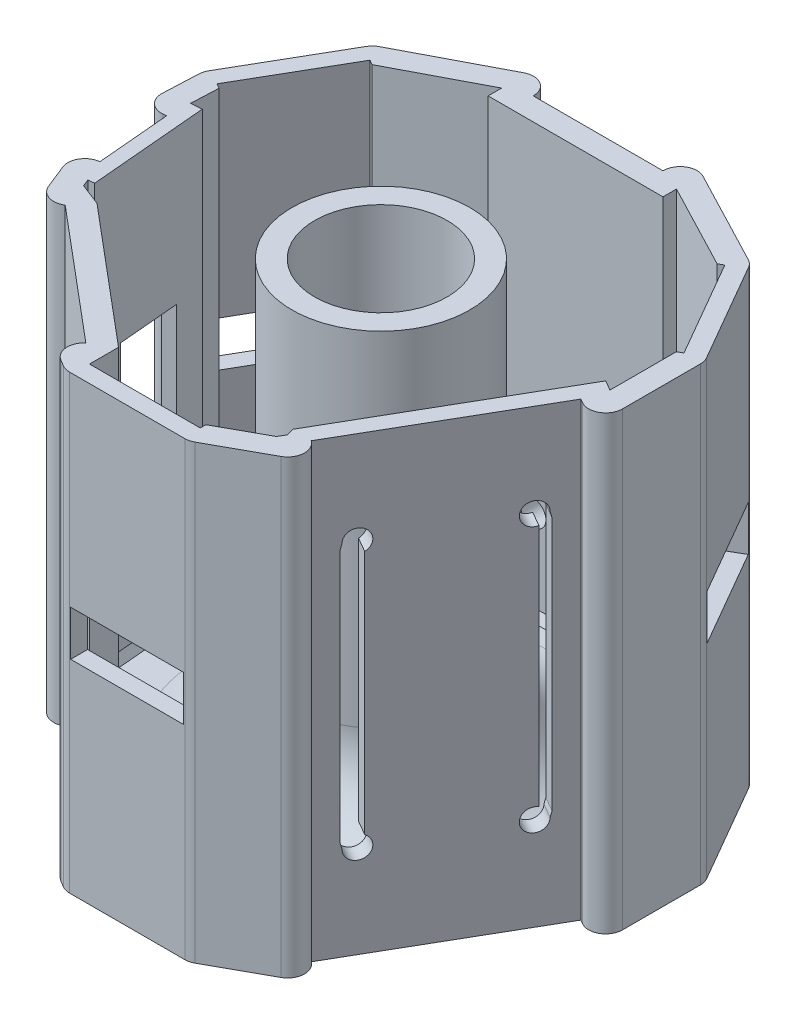
SolidWorks part; units mm, degrees
ref_plane "Alzado" through (0, 0, 0) normal (0, 0, 1) x (1, 0, 0)
ref_plane "Planta" through (0, 0, 0) normal (0, 1, 0) x (1, 0, 0)
ref_plane "Vista lateral" through (0, 0, 0) normal (1, 0, 0) x (0, 0, -1)
sketch "Croquis1" plane through (0, 0, 0) normal (0, 1, 0) x (1, 0, 0)
  line L0 (0, 0) -> (0, 45) construction
  line L8 (0, 0) -> (0, -45) construction
  line L9 (0, 0) -> (38.9711, 22.5) construction
  line L10 (0, 0) -> (-38.9711, 22.5) construction
  line L12 (-44.4711, 12.9737) -> (-33.4711, 32.0263)
  line L13 (33.4711, 32.0263) -> (44.4711, 12.9737)
  line L14 (-11, -45) -> (11, -45)
  line L19 (0, 0) -> (38.9711, -22.5) construction
  line L24 (0, 0) -> (-28.9254, -34.472) construction
  line L26 (0, 0) -> (-44.8288, -3.922) construction
  line L28 (44.4664, -6.9091) -> (44.4711, 12.9737)
  line L29 (33.4711, 32.0263) -> (11.5, 43.5057)
  line L30 (-11.5, 43.5057) -> (-33.4711, 32.0263)
  line L31 (-44.4711, 12.9737) -> (-44.9252, 2.5944)
  line L32 (-38.7871, -22.8159) -> (-43.7921, -10.3561)
  line L33 (-11, -45) -> (-15.827, -42.1249)
  line L34 (11, -45) -> (26.066, -36.682)
  line L36 (26.066, -36.682) -> (21.7702, -34.1233)
  line L37 (21.7702, -34.1233) -> (39.2695, -3.8137)
  line L38 (39.2695, -3.8137) -> (44.4664, -6.9091)
  line L39 (-38.7871, -22.8159) -> (-36.2125, -19.7545)
  line L40 (-36.2125, -19.7545) -> (-13.2559, -39.0607)
  line L41 (-13.2559, -39.0607) -> (-15.827, -42.1249)
  line L42 (-44.9252, 2.5944) -> (-40.9404, 2.943)
  line L43 (-40.9404, 2.943) -> (-39.8073, -10.0075)
  line L44 (-39.8073, -10.0075) -> (-43.7921, -10.3561)
  line L45 (-11.5, 43.5057) -> (-11.5, 38.5057)
  line L46 (-11.5, 38.5057) -> (11.5, 38.5057)
  line L47 (11.5, 38.5057) -> (11.5, 43.5057)
  circle A0 centre (0, 0) radius 45 construction
  circle A1 centre (0, 0) radius 11.75
  point P7 (-38.9711, 22.5)
  point P15 (0, 45)
  point P17 (38.9711, 22.5)
  point P20 (0, -45)
  point P31 (-28.9254, -34.472)
  point P35 (-44.8288, -3.922)
  point P38 (-40.3739, -3.5323)
  dimension "D1" = 90
  dimension "D2" = 23.5
  dimension "D13" = 4
  dimension "D3" = 120
  dimension "D4" = 120
  dimension "D5" = 23
  dimension "D6" = 22
  dimension "D7" = 22
  dimension "D8" = 22
  dimension "D9" = 35
  dimension "D10" = 5
  dimension "D11" = 34.9985
  dimension "D12" = 30
  dimension "D14" = 40
  dimension "D15" = 35
  dimension "D16" = 29.9956
  dimension "D17" = 4
  dimension "D18" = 13
  dimension "D19" = 23
  dimension "D20" = 5
extrude "Saliente-Extruir2" add sketch "Croquis1" along normal blind 80
shell "Vaciado1" thickness 4 removed face at (-6.4534, 80, 2.5494)
sketch "Croquis3" plane through (-40.3739, 0, 3.5323) normal (-0.9962, 0, 0.0872) x (0.0872, 0, 0.9962)
  line L0 (0, 80) -> (0, 40) construction
  line L2 (-6.5, 80) -> (6.5, 80) construction
  line L8 (5.5, 27.25) -> (-5.5, 27.25)
  line L9 (5.5, 27.25) -> (5.5, 52.75)
  line L10 (5.5, 52.75) -> (-5.5, 52.75)
  line L11 (-5.5, 27.25) -> (-5.5, 52.75)
  line L12 (5.5, 27.25) -> (-5.5, 52.75) construction
  line L13 (5.5, 52.75) -> (-5.5, 27.25) construction
  dimension "D1" = 40
  dimension "D2" = 11
  dimension "D3" = 25.5
extrude "Cortar-Extruir1" cut sketch "Croquis3" along normal blind 5 and the other way blind 5
sketch "Croquis5" plane through (-24.7325, 0, 29.409) normal (-0.6436, 0, 0.7653) x (0.7653, 0, 0.6436)
  line L0 (-0.0022, 80) -> (-0.0022, 40) construction
  line L1 (-15, 80) -> (14.9956, 80) construction
  line L3 (12.7478, 26.75) -> (-12.7522, 26.75)
  line L4 (12.7478, 26.75) -> (12.7478, 53.25)
  line L5 (12.7478, 53.25) -> (-12.7522, 53.25)
  line L6 (-12.7522, 26.75) -> (-12.7522, 53.25)
  line L7 (12.7478, 26.75) -> (-12.7522, 53.25) construction
  line L8 (12.7478, 53.25) -> (-12.7522, 26.75) construction
  dimension "D1" = 40
  dimension "D2" = 25.5
  dimension "D3" = 26.5
extrude "Cortar-Extruir3" cut sketch "Croquis5" against normal blind 5
sketch "Croquis6" plane through (0, 0, -38.5057) normal (0, 0, -1) x (-1, 0, 0)
  line L0 (0, 80) -> (0, 20) construction
  line L1 (-11.5, 80) -> (11.5, 80) construction
  line L2 (7.5, 20) -> (-7.5, 20) construction
  circle A0 centre (-7.5, 20) radius 2.25
  circle A1 centre (7.5, 20) radius 2.25
  point P8 (0, 20)
  dimension "D3" = 4.5
  dimension "D4" = 4.5
  dimension "D1" = 60
  dimension "D2" = 15
extrude "Cortar-Extruir4" cut sketch "Croquis6" against normal blind 5
sketch "Croquis7" plane through (31.1035, 0, 17.9576) normal (0.866, 0, 0.5) x (0.5, 0, -0.866)
  line L0 (-1.1673, 80) -> (-1.1673, 40) construction
  line L1 (-18.6665, 80) -> (16.332, 80) construction
  line L2 (-12.6673, 40) -> (-13.6673, 40) construction
  line L3 (10.3327, 16.5) -> (-12.6673, 16.5) construction
  line L4 (10.3327, 16.5) -> (10.3327, 63.5) construction
  line L5 (10.3327, 63.5) -> (-12.6673, 63.5) construction
  line L6 (-12.6673, 16.5) -> (-12.6673, 63.5) construction
  line L7 (10.3327, 16.5) -> (-12.6673, 63.5) construction
  line L8 (10.3327, 63.5) -> (-12.6673, 16.5) construction
  line L9 (10.3327, 40) -> (11.3327, 40) construction
  line L10 (-14.6673, 63.5) -> (-14.9148, 62.5451)
  line L12 (-11.7219, 18.2625) -> (-11.7219, 61.7375)
  line L14 (-14.9148, 17.5451) -> (-14.9148, 62.5451)
  line L15 (-12.6673, 21.9277) -> (-14.9148, 62.5451) construction
  line L16 (-12.6673, 58) -> (-14.9148, 17.5451) construction
  line L18 (10.8799, 18.4237) -> (10.8799, 61.5763)
  line L20 (12.5852, 17.4549) -> (12.5852, 62.4549)
  line L21 (10.3327, 22.072) -> (12.5852, 62.4549) construction
  line L22 (10.3327, 58) -> (12.5852, 17.4549) construction
  line L23 (12.3327, 63.5) -> (12.5852, 62.4549)
  line L24 (-14.6673, 16.5) -> (-14.9148, 17.5451)
  line L25 (12.3327, 16.5) -> (12.5852, 17.4549)
  arc A0 (-11.7219, 61.7375) -> (-14.6673, 63.5) centre (-12.6673, 63.5) ccw
  arc A1 (12.3327, 63.5) -> (10.8799, 61.5763) centre (10.3327, 63.5) ccw
  arc A2 (10.8799, 18.4237) -> (12.3327, 16.5) centre (10.3327, 16.5) ccw
  arc A3 (-14.6673, 16.5) -> (-11.7219, 18.2625) centre (-12.6673, 16.5) ccw
  dimension "D4" = 4
  dimension "D5" = 4
  dimension "D6" = 4
  dimension "D7" = 4
  dimension "D1" = 40
  dimension "D2" = 23
  dimension "D3" = 47
  dimension "D8" = 1
  dimension "D9" = 1
  dimension "D11" = 45
  dimension "D13" = 45
extrude "Cortar-Extruir5" cut sketch "Croquis7" against normal blind 5
sketch "Croquis8" plane through (38.9711, 0, -22.5) normal (0.866, 0, -0.5) x (-0.5, 0, -0.866)
  line L0 (0, 80) -> (0, 40) construction
  line L1 (-11, 80) -> (11, 80) construction
  line L3 (10, 36) -> (-10, 36)
  line L4 (10, 36) -> (10, 44)
  line L5 (10, 44) -> (-10, 44)
  line L6 (-10, 36) -> (-10, 44)
  line L7 (10, 36) -> (-10, 44) construction
  line L8 (10, 44) -> (-10, 36) construction
  dimension "D1" = 40
  dimension "D2" = 20
  dimension "D3" = 8
extrude "Cortar-Extruir6" cut sketch "Croquis8" against normal blind 3
pattern_circular "MatrizC1" count 3 over 360 about axis through (0, 80, 0) along (0, -1, 0) of "Cortar-Extruir6" reverse direction yes
fillet "Redondeo1" radius 3 14 edges at (-38.7871, 40, 22.8159) (-43.7921, 40, 10.3561) (-44.9252, 40, -2.5944) (-44.4711, 40, -12.9737) (-33.4711, 40, -32.0263) (-11.5, 40, -43.5057) (11.5, 40, -43.5057) (33.4711, 40, -32.0263) (44.4711, 40, -12.9737) (44.4664, 40, 6.9091) (26.066, 40, 36.682) (-15.827, 40, 42.1249) (11, 40, 45) (-11, 40, 45)
sketch "Croquis10" plane through (0, 80, 0) normal (0, 1, 0) x (1, 0, 0)
  line L1 (-9.6615, -36.857) -> (9.9691, -40)
  line L2 (9.9691, -40) -> (9.9691, -42)
  line L3 (9.9691, -42) -> (-9.6615, -42)
  line L4 (-40.5177, 11.8212) -> (-41.3838, 12.3212)
  line L5 (-41.3838, 12.3212) -> (-31.4544, 29.5194)
  line L6 (-31.4544, 29.5194) -> (-29.7223, 28.5194)
  line L7 (-29.7223, 28.5194) -> (-39.8577, 10.9645)
  line L8 (-39.8577, 10.9645) -> (-40.5177, 11.8212)
  line L9 (29.7223, 28.5194) -> (31.4544, 29.5194)
  line L10 (31.4544, 29.5194) -> (41.3369, 12.4024)
  line L11 (41.3369, 12.4024) -> (39.6049, 11.4024)
  line L12 (39.6049, 11.4024) -> (29.7223, 28.5194)
  line L13 (-36.6993, -14.1187) -> (-7.6234, -38.571) construction
  line L14 (-30.5884, 29.0194) -> (-40.5177, 11.8212) construction
  line L15 (-30.5884, 29.0194) -> (-40.5177, 11.8212) construction
  line L16 (16.9073, -36.5461) -> (39.1369, 1.9566)
  line L17 (40.4709, 11.9024) -> (30.5884, 29.0194) construction
  line L18 (40.4709, 11.9024) -> (30.5884, 29.0194) construction
  line L19 (-9.6615, -41) -> (9.9691, -41) construction
  line L20 (39.1369, 1.9566) -> (37.1645, 2.7234)
  line L22 (-9.6615, -42) -> (-9.6615, -41)
  line L23 (-9.6615, -41) -> (-9.6615, -36.857)
  line L25 (37.1645, 2.7234) -> (15.096, -35.5004)
  line L26 (15.096, -35.5004) -> (16.9073, -36.5461)
  line L27 (16.3331, -35.5406) -> (37.8328, 1.6979) construction
  line L28 (16.3331, -35.5406) -> (37.8328, 1.6979) construction
  line L29 (-37.5593, -15.1412) -> (-33.6887, -16.6506)
  line L30 (-33.6887, -16.6506) -> (-31.4544, -14.438)
  line L31 (-31.4544, -14.438) -> (-33.5382, 9.3799)
  line L32 (-33.5382, 9.3799) -> (-38.9095, 8.4146)
  line L33 (-38.9095, 8.4146) -> (-36.9536, -13.9417)
  line L34 (-36.9536, -13.9417) -> (-37.5593, -15.1412)
  line L35 (-37.3042, 7.2764) -> (-35.4739, -13.6437) construction
  line L36 (-37.3042, 7.2764) -> (-35.4739, -13.6437) construction
  point P12 (-30.5884, 29.0194)
  point P20 (30.5884, 29.0194)
  point P22 (40.4709, 11.9024)
  point P30 (9.9691, -41)
  dimension "D1" = 1
  dimension "D2" = 1
  dimension "D3" = 1
  dimension "D4" = 1
  dimension "D5" = 1.5
extrude "Cortar-Extruir7" cut sketch "Croquis10" against normal up to surface (76 mm away) up to face at (-5.7398, 4, 0.418)
sketch "Croquis12" plane through (0, 80, 0) normal (0, 1, 0) x (1, 0, 0)
  line L0 (18.0285, -36.5504) -> (18.7582, -35.3403)
  line L1 (18.7582, -35.3403) -> (17.8528, -31.9613)
  line L2 (17.8528, -31.9613) -> (15.4249, -36.1665)
  line L3 (15.4249, -36.1665) -> (18.0285, -36.5504)
  line L5 (17.1924, -36.0524) -> (38.692, 1.1861) construction
  line L6 (17.1924, -36.0524) -> (38.692, 1.1861) construction
  dimension "D1" = 45
  dimension "D2" = 1
extrude "Cortar-Extruir9" cut sketch "Croquis12" against normal up to surface (76 mm away) up to face at (-4.2658, 4, -1.1493)
fillet "Redondeo3" radius 15 1 edges at (0, 4, -15.75)
chamfer "Chaflán1" distance 1.5 angle 30 26 edges at (18.3933, 4, 35.9453) (13.9988, 4, 38.7752) (9.9691, 4, 41.5) (0.1538, 4, 42) (-9.6615, 4, 39.4285) (-21.6751, 4, 26.7538) (-35.624, 4, 15.8959) (-37.5189, 4, 13.8226) (-37.8834, 4, 3.3144) (-39.7641, 4, -7.0612) (-40.6237, 4, -9.399) (-40.9507, 4, -12.0712) (-36.4191, 4, -20.9203) (-31.0214, 4, -29.2694) (-23.0442, 4, -32.9611) (-15.5, 4, -35.7043) (0, 4, -34.5057) (15.5, 4, -35.7043) (23.0442, 4, -32.9611) (31.0214, 4, -29.2694) (36.3956, 4, -20.9609) (40.9039, 4, -12.1524) (40.4695, 4, -6.0153) (39.5801, 4, -0.6571) (28.5421, 4, 16.3941) (18.5752, 4, 34.6572) first distance on face at (18.3933, 42, 35.9453) first distance on face at (13.9988, 42, 38.7752) first distance on face at (9.9691, 41.3333, 41.6667) first distance on face at (0.1538, 20, 42) first distance on face at (-9.6615, 41.3333, 40.2857) first distance on face at (-21.6751, 42, 26.7538) first distance on face at (-35.624, 42, 15.8959) first distance on face at (-37.5189, 42, 13.8226) first distance on face at (-37.8834, 42, 3.3144) first distance on face at (-39.7641, 42, -7.0612) first distance on face at (-40.6237, 42, -9.399) first distance on face at (-40.9507, 42, -12.0712) first distance on face at (-36.4164, 41, -20.9249) first distance on face at (-31.1657, 41.3333, -29.3527) first distance on face at (-23.0442, 42, -32.9611) first distance on face at (-15.5, 42, -35.7043) first distance on face at (9.75, 20, -34.5057) first distance on face at (15.5, 42, -35.7043) first distance on face at (23.0442, 42, -32.9611) first distance on face at (31.1657, 41.3333, -29.3527) first distance on face at (36.3956, 20, -20.9609) first distance on face at (41.0482, 41.3333, -12.2357) first distance on face at (40.4695, 42, -6.0153) first distance on face at (39.5801, 42, -0.6571) first distance on face at (28.5421, 42, 16.3941) first distance on face at (18.5752, 42, 34.6572)
